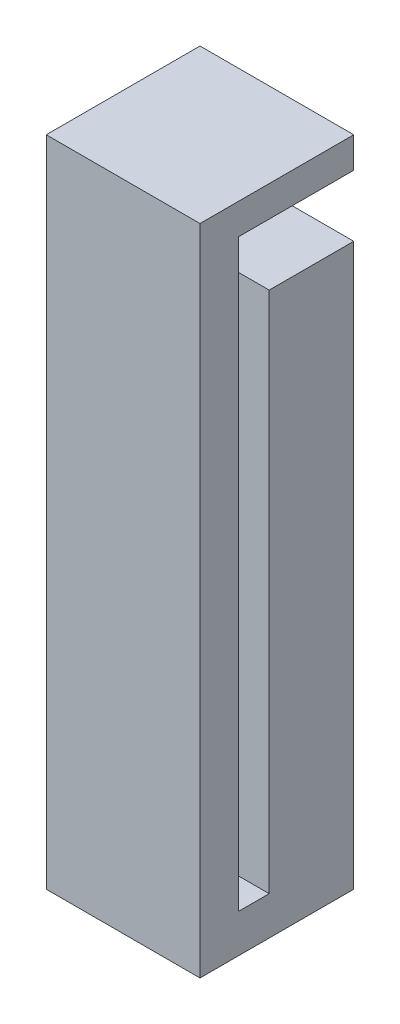
SolidWorks part; units mm, degrees
ref_plane "Front Plane" through (0, 0, 0) normal (0, 0, 1) x (1, 0, 0)
ref_plane "Top Plane" through (0, 0, 0) normal (0, 1, 0) x (1, 0, 0)
ref_plane "Right Plane" through (0, 0, 0) normal (1, 0, 0) x (0, 0, -1)
sketch "Sketch1" plane through (0, 0, 0) normal (0, 1, 0) x (1, 0, 0)
  line L1 (0, 0) -> (10, 0)
  line L2 (0, 0) -> (0, 10)
  line L3 (0, 10) -> (10, 10)
  line L4 (10, 0) -> (10, 10)
  dimension "D1" = 10
extrude "Boss-Extrude1" add sketch "Sketch1" along normal blind 40
sketch "Sketch3" plane through (0, 0, -10) normal (0, 0, -1) x (-1, 0, 0)
  line L0 (-10, 40) -> (-10, 0) construction
  line L1 (-2.5, 38) -> (-10, 38)
  line L2 (-2.5, 38) -> (-2.5, 34)
  line L3 (-2.5, 34) -> (-10, 34)
  line L4 (-10, 38) -> (-10, 34)
  line L5 (-10, 40) -> (0, 40) construction
  line L6 (0, 40) -> (0, 0) construction
  dimension "D1" = 2
  dimension "D2" = 4
  dimension "D3" = 2.5
extrude "Cut-Extrude1" cut sketch "Sketch3" against normal offset from surface (7.5 mm away) 2.5 up to face at (5, 20, 0)
sketch "Sketch4" plane through (0, 0, 0) normal (0, -1, 0) x (1, 0, 0)
  line L0 (2.5, -2.5) -> (2.5, -10) construction
  line L1 (2.5, -2.5) -> (2.5, -10)
  line L2 (2.5, -2.5) -> (10, -2.5) construction
  line L3 (2.5, -2.5) -> (10, -2.5)
  line L4 (10, -10) -> (0, -10) construction
  line L5 (10, -2.5) -> (2.5, -2.5)
  line L6 (10, -2.5) -> (10, -4.5)
  line L7 (10, -4.5) -> (2.5, -4.5)
  line L8 (2.5, -2.5) -> (2.5, -4.5)
  line L9 (4.5, -10) -> (2.5, -10)
  line L10 (4.5, -10) -> (4.5, -4.5)
  line L11 (4.5, -4.5) -> (2.5, -4.5)
  line L12 (2.5, -10) -> (2.5, -4.5)
  line M10 (0, -10) -> (10, -10)
  line M11 (10, -10) -> (10, 0)
  dimension "D1" = 2
  dimension "D2" = 2
extrude "Cut-Extrude2" cut sketch "Sketch4" against normal up to surface (38 mm away) contours L7 L3 L1 M11 | L10 L7 L1 M10 region at (6.25, 0, -3.5) region at (3.5, 0, -7.25) up to face at (6.25, 38, -6.25)
sketch "Sketch5" plane through (0, 0, 0) normal (0, -1, 0) x (1, 0, 0)
  line L1 (0, 0) -> (10, 0)
  line L2 (0, 0) -> (0, -10)
  line L3 (0, -10) -> (10, -10)
  line L4 (10, 0) -> (10, -10)
extrude "Boss-Extrude2" add sketch "Sketch5" along normal blind 2.5
sketch "Sketch6" plane through (0, 0, 0) normal (0, 1, 0) x (1, 0, 0)
  line L0 (10, 4.5) -> (4.5, 4.5) construction
  line L1 (2.5, 2.5) -> (6.5, 2.5)
  line L2 (2.5, 2.5) -> (2.5, 4.5)
  line L3 (2.5, 4.5) -> (6.5, 4.5)
  line L4 (6.5, 2.5) -> (6.5, 4.5)
  line L5 (4.5, 10) -> (4.5, 4.5) construction
  line L6 (2.5, 4.5) -> (4.5, 4.5)
  line L7 (2.5, 4.5) -> (2.5, 6.5)
  line L8 (2.5, 6.5) -> (4.5, 6.5)
  line L9 (4.5, 4.5) -> (4.5, 6.5)
  line L10 (3.5, 2.5) -> (3.5, 6.5) construction
  line M7 (10, 4.5) -> (4.5, 4.5)
  line M8 (4.5, 4.5) -> (4.5, 10)
  line M10 (2.5, 10) -> (2.5, 2.5)
  line M11 (2.5, 2.5) -> (10, 2.5)
  dimension "D1" = 4
extrude "Boss-Extrude3" add sketch "Sketch6" along normal up to surface (38 mm away) contours L10 L1 L4 L6 M7 | L10 L6 L8 M8 | L3 L10 L8 M10 | L10 L3 M11 M10 region at (3, 0, -3.5) region at (5, 0, -3.5) region at (3, 0, -5.5) region at (4, 0, -5.5) up to face at (6.25, 38, -6.25)
sketch "Sketch7" plane through (0, -2.5, 0) normal (0, -1, 0) x (1, 0, 0)
  line L0 (0, -5) -> (10, -5) construction
  line L1 (0, 0) -> (0, -10) construction
  line L2 (10, -10) -> (10, 0) construction
  circle A0 centre (5, -5) radius 2.125
  dimension "D1" = 4.25
extrude "Cut-Extrude3" cut sketch "Sketch7" against normal blind 2.25
